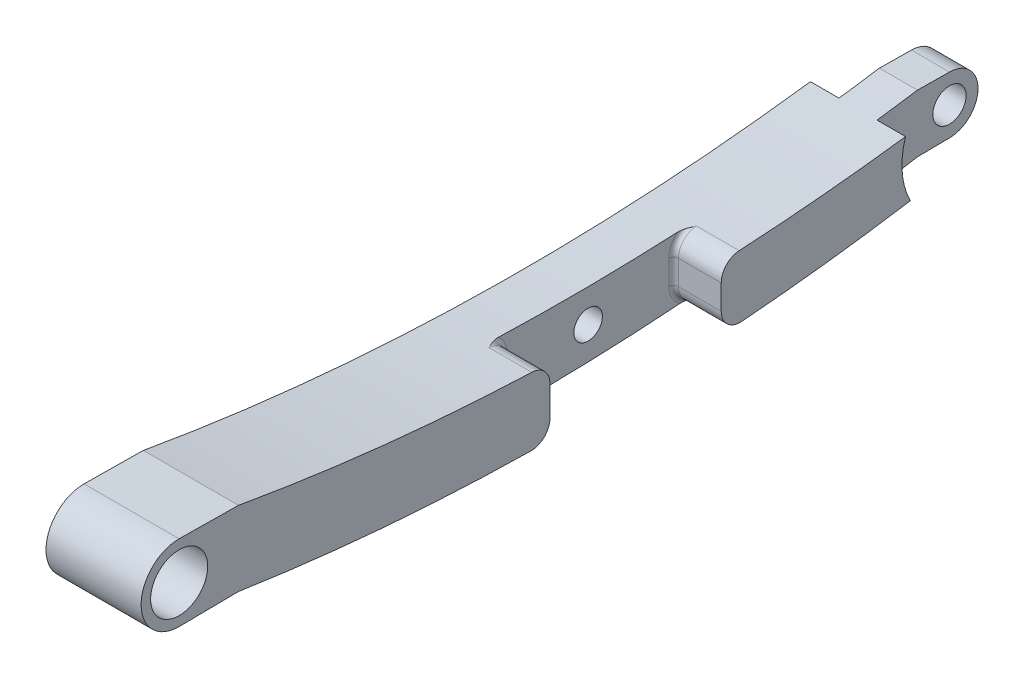
SolidWorks part; units mm, degrees
ref_plane "Front Plane" through (0, 0, 0) normal (0, 0, 1) x (1, 0, 0)
ref_plane "Top Plane" through (0, 0, 0) normal (0, 1, 0) x (1, 0, 0)
ref_plane "Right Plane" through (0, 0, 0) normal (1, 0, 0) x (0, 0, -1)
sketch "Sketch2" plane through (0, 0, 0) normal (1, 0, 0) x (0, 0, -1)
  line L0 (-85.4745, 5.9993) -> (-1.4745, 5.9993) construction
  line L5 (-103.8806, -24.3212) -> (15.5737, -24.3212) construction
  line L11 (-85.4745, 9.9993) -> (-79.2389, 9.925)
  line L12 (-85.4745, 1.9993) -> (-79.2389, 2.0735)
  line L13 (-4.847, 2.9591) -> (-1.4745, 2.9993)
  line L14 (-4.847, 9.0394) -> (-1.4745, 8.9993)
  circle A12 centre (-85.4745, 5.9993) radius 3
  circle A13 centre (-1.4745, 5.9993) radius 1.75
  arc A14 (-85.4745, 9.9993) -> (-85.4745, 1.9993) centre (-85.4745, 5.9993) ccw
  arc A15 (-1.4745, 2.9993) -> (-1.4745, 8.9993) centre (-1.4745, 5.9993) ccw
  arc A16 (-4.847, 9.0394) -> (-79.2389, 9.925) centre (-39.3411, 236.4381) cw
  arc A17 (-79.2389, 2.0735) -> (-4.847, 2.9591) centre (-44.7448, 229.4722) ccw
extrude "Boss-Extrude2" add sketch "Sketch2" along normal blind 10
ref_plane "Plane1" through (0, 0, 1.4745) normal (0, 0, 1) x (1, 0, 0)
sketch "Sketch4" plane through (0, 0, 1.4745) normal (0, 0, 1) x (1, 0, 0)
  line L0 (0, 8.9993) -> (0, 2.9993) construction
  line L1 (0, 5.9993) -> (3, 5.9993)
  line L2 (0, 5.9993) -> (0, 13.9993)
  line L3 (0, 13.9993) -> (3, 13.9993)
  line L4 (3, 5.9993) -> (3, 13.9993)
  line L5 (10, 2.9993) -> (10, 8.9993) construction
  line L6 (10, 5.9993) -> (7, 5.9993)
  line L7 (10, 5.9993) -> (10, 13.9993)
  line L8 (10, 13.9993) -> (7, 13.9993)
  line L9 (7, 5.9993) -> (7, 13.9993)
  dimension "D1" = 3
  dimension "D2" = 3
  dimension "D3" = 8
  dimension "D4" = 8
revolve "Cut-Revolve1" cut sketch "Sketch4" angle 360 about axis through (10, 5.9993, 1.4745) along (-1, 0, 0)
sketch "Sketch5" plane through (10, 0, 0) normal (1, 0, 0) x (0, 0, -1)
  circle A0 centre (-37.4745, 2.9993) radius 1.5
  dimension "D3" = 3
  dimension "D1" = 48
  dimension "D2" = 3
extrude "Cut-Extrude1" cut sketch "Sketch5" against normal blind 10
sketch "Sketch6" plane through (0, 0, 0) normal (0, 1, 0) x (1, 0, 0)
  line L0 (10, -79.2389) -> (10, -9.0945) construction
  line L1 (10, -28.4745) -> (5, -28.4745)
  line L2 (10, -28.4745) -> (10, -46.4745)
  line L3 (10, -46.4745) -> (5, -46.4745)
  line L4 (5, -28.4745) -> (5, -46.4745)
  line L7 (0, -37.4745) -> (10, -37.4745) construction
  point P8 (5, -37.4745)
  dimension "D1" = 5
  dimension "D2" = 18
  dimension "D3" = 0
extrude "Cut-Extrude2" cut sketch "Sketch6" against normal through all both and the other way through all
fillet "Fillet2" radius 2 4 edges at (7.5, 6.5487, 46.4745) (7.5, -0.5213, 46.4745) (7.5, 6.6949, 28.4745) (7.5, 0.0484, 28.4745)
fillet "Fillet3" radius 0.5 6 edges at (5, 0.0769, 47.0719) (5, 6.004, 47.0327) (5, 6.1696, 27.9274) (5, 3.5003, 28.4745) (5, 3.0603, 46.4745) (5, 0.7356, 27.8308)
